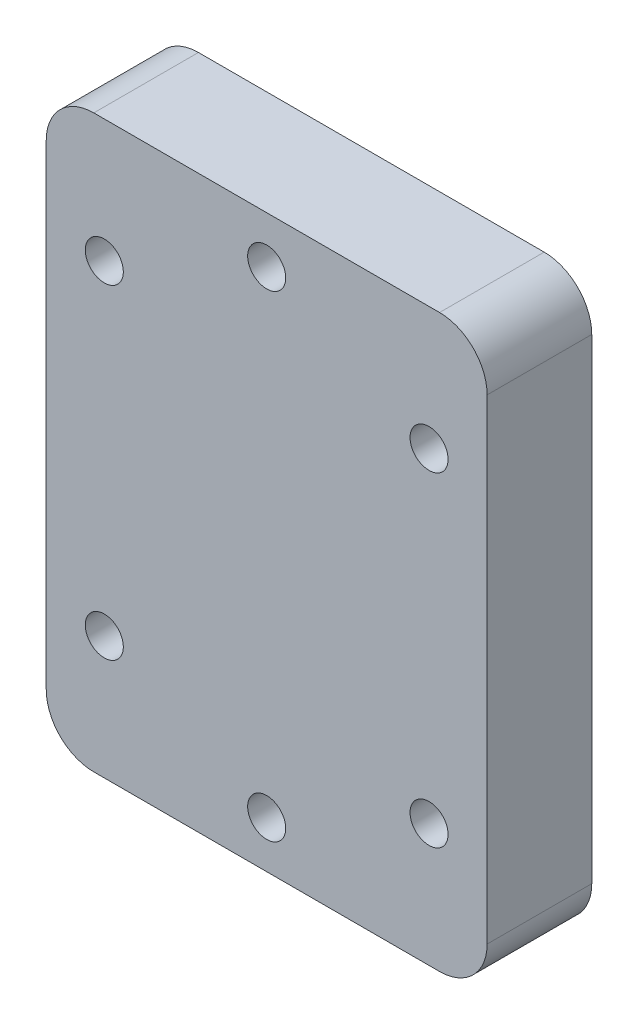
SolidWorks part; units mm, degrees
material "ABS"
ref_plane "X-Y Datum" through (0, 0, 0) normal (0, 0, 1) x (1, 0, 0)
ref_plane "X-Z Datum" through (0, 0, 0) normal (0, 1, 0) x (1, 0, 0)
ref_plane "Y-Z Datum" through (0, 0, 0) normal (1, 0, 0) x (0, 0, -1)
sketch "Sketch1" plane through (0, 0, 0) normal (0, 0, 1) x (1, 0, 0)
  line L0 (0, 30) -> (0, 20.1212) construction
  line L1 (-23.175, 0) -> (23.175, 0) construction
  line L4 (-20, 20) -> (-20, -20) construction
  line L5 (-23.175, -30) -> (23.175, -30)
  line L6 (-23.175, -30) -> (-23.175, 30)
  line L7 (-23.175, 30) -> (23.175, 30)
  line L8 (23.175, -30) -> (23.175, 30)
  line L9 (-23.175, -30) -> (23.175, 30) construction
  line L10 (-23.175, 30) -> (23.175, -30) construction
  line L11 (20, 20) -> (-20, 20) construction
  line L12 (-23.175, 20.1212) -> (23.175, 20.1212) construction
  circle A0 centre (0, 25.0606) radius 2
  circle A1 centre (0, -25.0606) radius 2
  circle A2 centre (17.0711, 17.0711) radius 2 construction
  circle A3 centre (17.0711, -17.0711) radius 2 construction
  circle A4 centre (-17.0711, -17.0711) radius 2 construction
  circle A5 centre (-17.0711, 17.0711) radius 2 construction
  circle A6 centre (17.0711, 17.0711) radius 2
  circle A7 centre (17.0711, -17.0711) radius 2
  circle A8 centre (-17.0711, -17.0711) radius 2
  circle A9 centre (-17.0711, 17.0711) radius 2
  point P2 (0, 0)
  dimension "D3" = 4
  dimension "D1" = 3.175
  dimension "D2" = 10
  dimension "D4" = 4.9394
extrude "Boss-Extrude1" add sketch "Sketch1" against normal blind 9 and the other way blind 2 contours L5 L8 L7 L6 A9 A8 A7 A6 A0 A1 region at (0, 0, 0)
sketch "Sketch2" plane through (0, 0, -9) normal (0, 0, -1) x (-1, 0, 0)
  line L1 (-15, -15) -> (15, -15)
  line L2 (-15, -15) -> (-15, 15)
  line L3 (-15, 15) -> (15, 15)
  line L4 (15, -15) -> (15, 15)
  line L5 (-15, -15) -> (15, 15) construction
  line L6 (-15, 15) -> (15, -15) construction
  point P0 (0, 0)
  dimension "D1" = 30
  dimension "D2" = 30
extrude "Cut-Extrude1" cut sketch "Sketch2" against normal blind 6.35
sketch "Sketch4" plane through (0, 0, -9) normal (0, 0, -1) x (-1, 0, 0)
  circle A0 centre (-17.0711, 17.0711) radius 2
  circle A1 centre (17.0711, 17.0711) radius 2
  circle A2 centre (-17.0711, -17.0711) radius 2
  circle A3 centre (17.0711, -17.0711) radius 2
extrude "Boss-Extrude4" add sketch "Sketch4" against normal blind 0.85
fillet "Fillet1" radius 5 4 edges at (23.175, 30, -3.5) (-23.175, 30, -3.5) (-23.175, -30, -3.5) (23.175, -30, -3.5)
